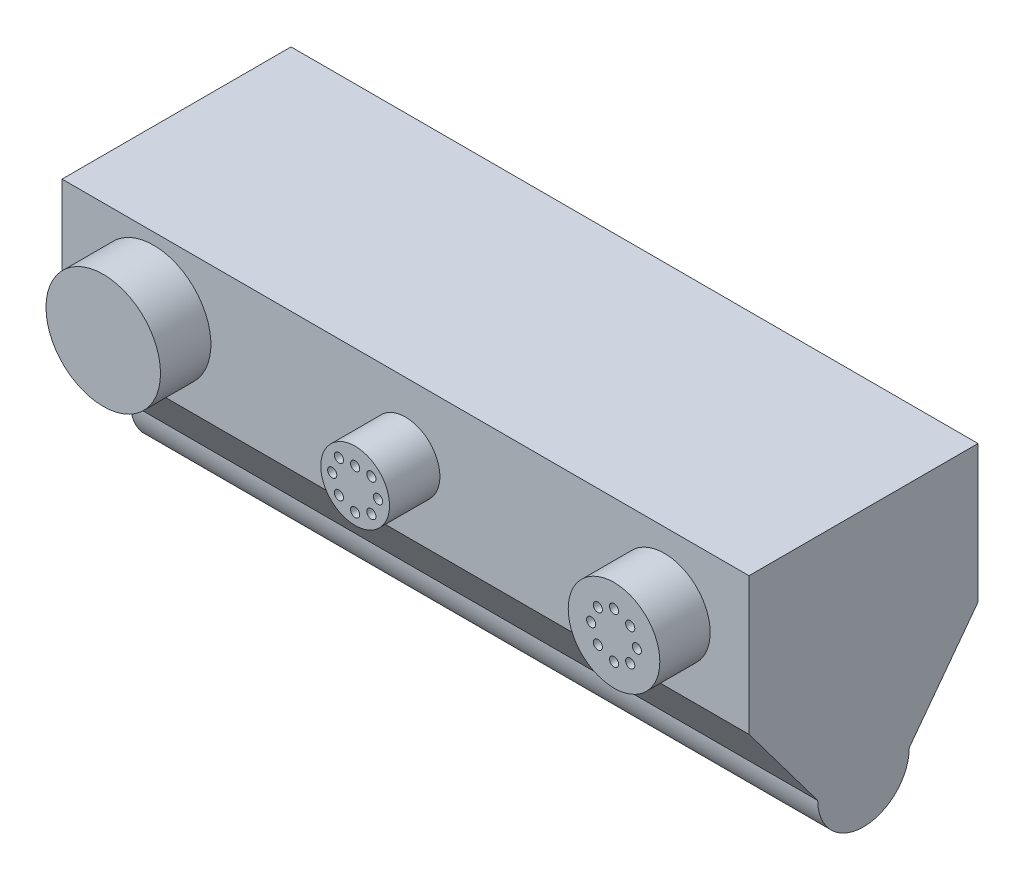
SolidWorks part; units mm, degrees
ref_plane "Ebene vorne" through (0, 0, 0) normal (0, 0, 1) x (1, 0, 0)
ref_plane "Ebene oben" through (0, 0, 0) normal (0, 1, 0) x (1, 0, 0)
ref_plane "Ebene rechts" through (0, 0, 0) normal (1, 0, 0) x (0, 0, -1)
sketch "Skizze1" plane through (0, 0, 0) normal (0, 1, 0) x (1, 0, 0)
  line L1 (-75, 25) -> (75, 25)
  line L2 (-75, 25) -> (-75, -25)
  line L3 (-75, -25) -> (75, -25)
  line L4 (75, 25) -> (75, -25)
  line L5 (-75, 25) -> (75, -25) construction
  line L6 (-75, -25) -> (75, 25) construction
  point P0 (0, 0)
  dimension "D1" = 50
  dimension "D2" = 150
extrude "Aufsatz-Linear austragen1" add sketch "Skizze1" along normal blind 50
sketch "Skizze2" plane through (75, 0, 0) normal (1, 0, 0) x (0, 0, -1)
  circle A0 centre (0, 0) radius 10
  point P3 (0, 0)
  dimension "D1" = 20
extrude "Aufsatz-Linear austragen2" add sketch "Skizze2" against normal up to surface (150 mm away) up to face at (-75, 25, 0)
sketch "Skizze3" plane through (75, 0, 0) normal (1, 0, 0) x (0, 0, -1)
  line L0 (-10, 0) -> (-25, 20)
  line L1 (-25, 50) -> (-25, 0) construction
  line L2 (-25, 20) -> (-25, 0)
  line L3 (-25, 0) -> (-10, 0)
  line L4 (0, 33) -> (0, -33) construction
  line L5 (25, 20) -> (25, 0)
  line L6 (10, 0) -> (25, 20)
  line L7 (25, 0) -> (10, 0)
  dimension "D1" = 20
extrude "Schnitt-Linear austragen1" cut sketch "Skizze3" against normal blind 182
sketch "Skizze4" plane through (0, 0, 25) normal (0, 0, 1) x (1, 0, 0)
  line L0 (-75, 35) -> (75, 35) construction
  line L1 (-75, 50) -> (-75, 20) construction
  line L2 (75, 50) -> (75, 20) construction
  line L3 (56.5262, 35) -> (56.5262, 45) construction
  line L5 (0, 35) -> (0, 42.5) construction
  circle A0 centre (-55, 35) radius 12.5
  circle A1 centre (56.5262, 35) radius 10
  circle A2 centre (56.5262, 40) radius 1
  circle A3 centre (60.0617, 38.5355) radius 1
  circle A4 centre (61.5262, 35) radius 1
  circle A5 centre (60.0617, 31.4645) radius 1
  circle A6 centre (56.5262, 30) radius 1
  circle A7 centre (52.9907, 31.4645) radius 1
  circle A8 centre (51.5262, 35) radius 1
  circle A9 centre (52.9907, 38.5355) radius 1
  circle A19 centre (0, 35) radius 7.5
  circle A20 centre (0, 38.75) radius 1
  circle A21 centre (3.5355, 38.5355) radius 1
  circle A22 centre (5, 35) radius 1
  circle A23 centre (3.5355, 31.4645) radius 1
  circle A24 centre (0, 30) radius 1
  circle A25 centre (-3.5355, 31.4645) radius 1
  circle A26 centre (-5, 35) radius 1
  circle A27 centre (-3.5355, 38.5355) radius 1
  point P30 (56.5262, 35)
  point P70 (0, 35)
  dimension "D1" = 25
  dimension "D3" = 20
  dimension "D4" = 2
  dimension "D6" = 15
  dimension "D2" = 20
  dimension "D5" = 8
extrude "Aufsatz-Linear austragen3" add sketch "Skizze4" along normal blind 11
